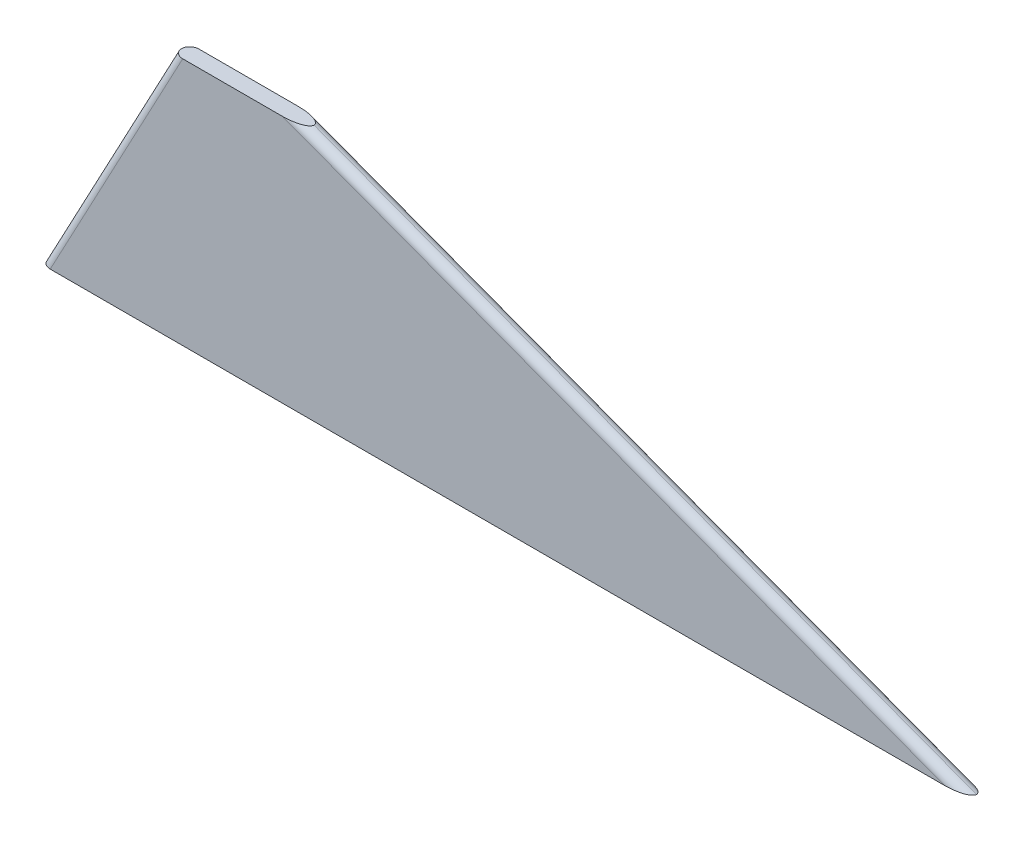
SolidWorks part; units mm, degrees
ref_plane "Front Plane" through (0, 0, 0) normal (0, 0, 1) x (1, 0, 0)
ref_plane "Top Plane" through (0, 0, 0) normal (0, 1, 0) x (1, 0, 0)
ref_plane "Right Plane" through (0, 0, 0) normal (1, 0, 0) x (0, 0, -1)
sketch "Sketch1" plane through (0, 0, 0) normal (0, 0, 1) x (1, 0, 0)
  line L0 (0, 0) -> (-355.6, 0)
  line L1 (-355.6, 0) -> (-304.8, 95.25)
  line L2 (-304.8, 95.25) -> (-254, 95.25)
  line L3 (-254, 95.25) -> (0, 0)
  dimension "D1" = 50.8
  dimension "D2" = 355.6
  dimension "D3" = 95.25
  dimension "D4" = 50.8
extrude "Boss-Extrude1" add sketch "Sketch1" along normal blind 6.35
fillet "Fillet1" radius 3.175 4 edges at (-330.2, 47.625, 6.35) (-330.2, 47.625, 0) (-127, 47.625, 6.35) (-127, 47.625, 0)
